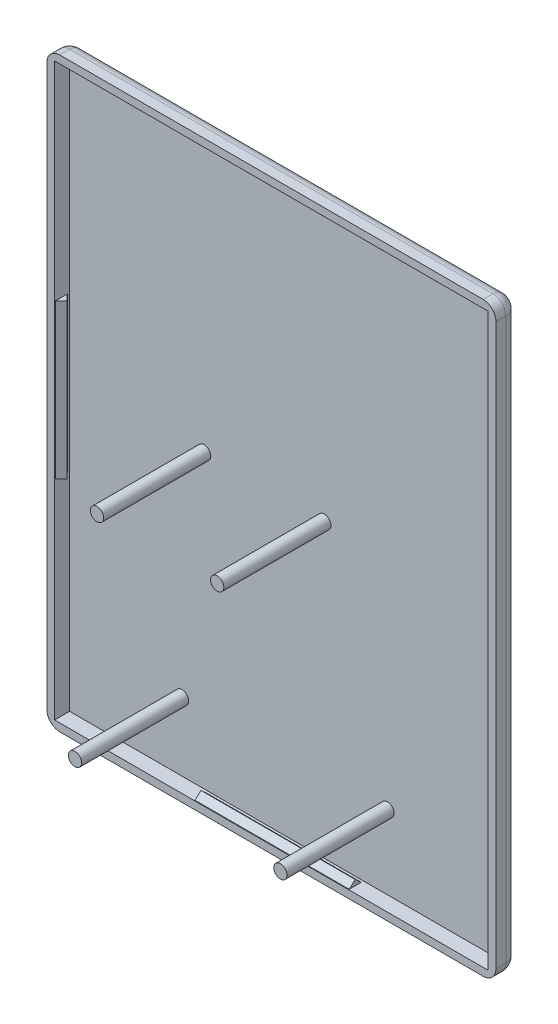
SolidWorks part; units mm, degrees
ref_plane "Plan de face" through (0, 0, 0) normal (0, 0, 1) x (1, 0, 0)
ref_plane "Plan de dessus" through (0, 0, 0) normal (0, 1, 0) x (1, 0, 0)
ref_plane "Plan de droite" through (0, 0, 0) normal (1, 0, 0) x (0, 0, -1)
sketch "Esquisse1" plane through (0, 0, 0) normal (0, 0, 1) x (1, 0, 0)
  line L1 (-50.6, -66.6) -> (50.6, -66.6)
  line L2 (-50.6, -66.6) -> (-50.6, 66.6)
  line L3 (-50.6, 66.6) -> (50.6, 66.6)
  line L4 (50.6, -66.6) -> (50.6, 66.6)
  line L5 (-50.6, -66.6) -> (50.6, 66.6) construction
  line L6 (-50.6, 66.6) -> (50.6, -66.6) construction
  point P0 (0, 0)
  dimension "D1" = 101.2
  dimension "D2" = 133.2
extrude "Boss.-Extru.1" add sketch "Esquisse1" against normal blind 3.5
shell "Coque1" thickness 1.8 removed face at (0, 0, 0) outward yes
fillet "Congé4" radius 3 8 edges at (-52.4, -68.4, -2.65) (52.4, 68.4, -2.65) (52.4, -68.4, -2.65) (0, -68.4, -5.3) (-52.4, 0, -5.3) (0, 68.4, -5.3) (52.4, 0, -5.3) (-52.4, 68.4, -2.65)
sketch3d "Esquisse3D1"
  line L5 (50.6, 0, 0) -> (50.6, 0, -0.15) construction
  line L8 (50.6, 0, -0.15) -> (50.6, 0, -2.95)
  line L10 (50.6, -66.6, 0) -> (50.6, 66.6, 0) construction
  line L11 (50.6, 0, -2.95) -> (49.3155, 0, -1.55)
  line L12 (49.3155, 0, -1.55) -> (50.6, 0, -0.15)
  dimension "D1" = 0.15
  dimension "D3" = 1.9
  dimension "D2" = 2.8
extrude "Boss.-Extru.2" add sketch "Esquisse3D1" along direction (0, 1, 0) on the side of the normal blind 18 and the other way blind 18
mirror "Symétrie1" about plane through (0, 0, 0) normal (1, 0, 0) of "Boss.-Extru.2"
sketch3d "Esquisse3D2"
  line L0 (50.6, 66.6, 0) -> (-50.6, 66.6, 0) construction
  line L1 (0, 66.6, -0.15) -> (0, 66.6, -2.95)
  line L2 (0, 66.6, 0) -> (0, 66.6, -0.15) construction
  line L5 (50.6, 66.6, -3.5) -> (50.6, 66.6, 0) construction
  line L6 (0, 66.6, -2.95) -> (0, 65.3155, -1.55)
  line L7 (0, 65.3155, -1.55) -> (0, 66.6, -0.15)
  dimension "D1" = 0.15
  dimension "D2" = 2.8
  dimension "D3" = 1.9
extrude "Boss.-Extru.3" add sketch "Esquisse3D2" along direction (-1, 0, 0) on the side of the normal blind 18 and the other way blind 18
mirror "Symétrie2" about plane through (0, 0, 0) normal (0, 1, 0) of "Boss.-Extru.3"
sketch "Esquisse5" plane through (0, 0, -3.5) normal (0, 0, 1) x (1, 0, 0)
  line L0 (0, -30.31) -> (-50.6, -30.31) construction
  line L1 (-26.515, 3.98) -> (26.515, 3.98) construction
  line L2 (-26.515, 3.98) -> (-26.515, -64.6) construction
  line L3 (-26.515, -64.6) -> (26.515, -64.6) construction
  line L4 (26.515, 3.98) -> (26.515, -64.6) construction
  line L5 (-26.515, 3.98) -> (26.515, -64.6) construction
  line L6 (-26.515, -64.6) -> (26.515, 3.98) construction
  line L7 (-50.6, 66.6) -> (-50.6, -66.6) construction
  line L8 (0, -30.31) -> (50.6, -30.31) construction
  line L9 (50.6, -66.6) -> (50.6, 66.6) construction
  line L11 (-50.6, -66.6) -> (50.6, -66.6) construction
  circle A0 centre (-24.345, -50.63) radius 1.55
  circle A1 centre (23.585, -49.36) radius 1.55
  circle A2 centre (8.835, 1.44) radius 1.55
  circle A3 centre (-19.205, 1.44) radius 1.55
  dimension "D4" = 17.68
  dimension "D11" = 2
  dimension "D1" = 53.03
  dimension "D2" = 68.58
  dimension "D3" = 13.97
  dimension "D5" = 66.04
  dimension "D6" = 45.72
  dimension "D7" = 66.04
  dimension "D8" = 50.1
  dimension "D9" = 15.24
  dimension "D10" = 47.93
extrude "Boss.-Extru.4" add sketch "Esquisse5" along normal blind 25
